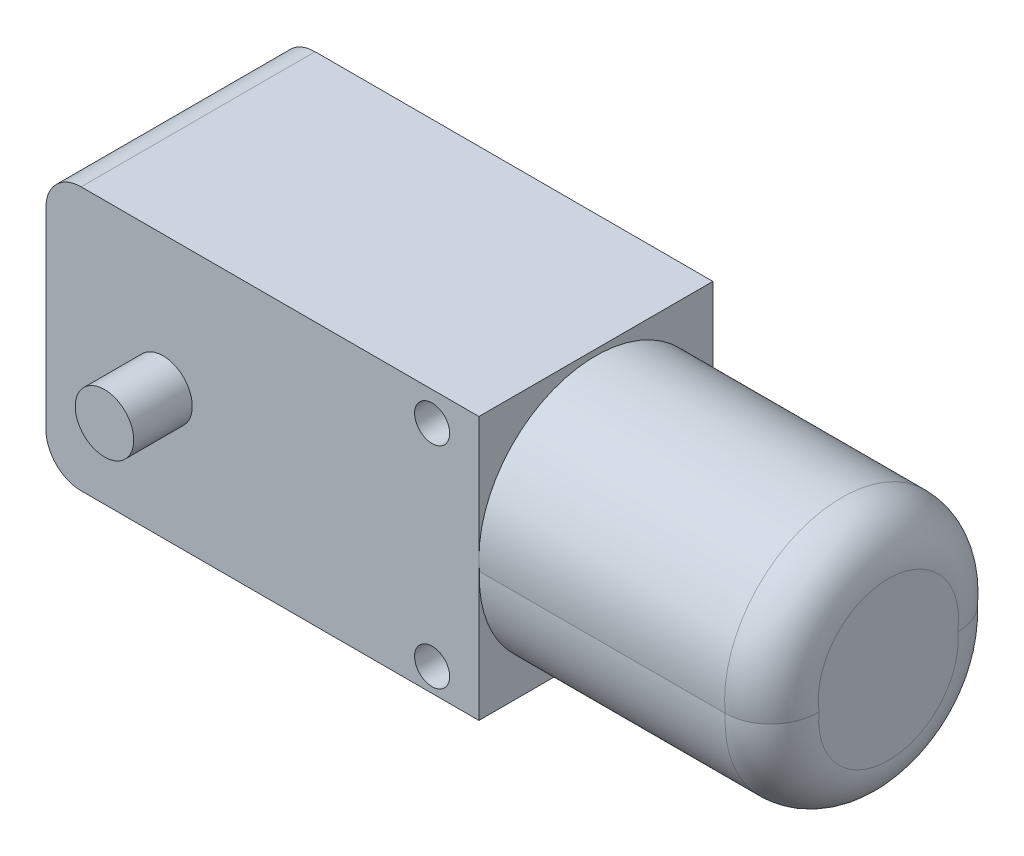
SolidWorks part; units mm, degrees
ref_plane "Front Plane" through (0, 0, 0) normal (0, 0, 1) x (1, 0, 0)
ref_plane "Top Plane" through (0, 0, 0) normal (0, 1, 0) x (1, 0, 0)
ref_plane "Right Plane" through (0, 0, 0) normal (1, 0, 0) x (0, 0, -1)
sketch "Sketch1" plane through (0, 0, 0) normal (0, 0, 1) x (1, 0, 0)
  line L1 (-64.2641, -2.5) -> (-27.2641, -2.5)
  line L2 (-64.2641, -2.5) -> (-64.2641, -25)
  line L3 (-64.2641, -25) -> (-27.2641, -25)
  line L4 (-27.2641, -2.5) -> (-27.2641, -25)
  dimension "D1" = 22.5
  dimension "D2" = 37
extrude "Boss-Extrude1" add sketch "Sketch1" against normal blind 20
sketch "Sketch2" plane through (-27.2641, 0, 0) normal (1, 0, 0) x (0, 0, -1)
  line L0 (20, -25) -> (0, -25) construction
  line L1 (20, -2.5) -> (0, -2.5) construction
  arc A0 (0.0501, -14) -> (19.9499, -14) centre (10, -14.5) ccw
  arc A1 (19.9499, -14) -> (0.0501, -14) centre (10, -13) ccw
  dimension "D2" = 12
  dimension "D1" = 12
extrude "Boss-Extrude2" add sketch "Sketch2" along normal blind 25
sketch "Sketch3" plane through (0, 0, 0) normal (0, 0, 1) x (1, 0, 0)
  circle A0 centre (-54.2641, -14) radius 2.5
  dimension "D1" = 5
extrude "Boss-Extrude3" add sketch "Sketch3" along normal blind 5
sketch "Sketch4" plane through (0, 0, -20) normal (0, 0, -1) x (-1, 0, 0)
  circle A1 centre (54.2641, -14) radius 2.5
  circle A2 centre (54.2641, -14) radius 2.5
  dimension "D1" = 0
extrude "Boss-Extrude4" add sketch "Sketch4" along normal blind 5
fillet "Fillet1" radius 3 2 edges at (-64.2641, -2.5, -10) (-64.2641, -25, -10)
fillet "Fillet2" radius 4 2 edges at (-2.2641, -3, -10) (-2.2641, -24.4624, -10)
sketch "Sketch5" plane through (-64.2641, 0, 0) normal (-1, 0, 0) x (0, 0, 1)
  line L0 (-10, -25) -> (-10, -2.5) construction
  line L1 (-8.625, -16.25) -> (-11.375, -16.25)
  line L2 (-8.625, -16.25) -> (-8.625, -11.25)
  line L3 (-8.625, -11.25) -> (-11.375, -11.25)
  line L4 (-11.375, -16.25) -> (-11.375, -11.25)
  line L5 (0, -25) -> (-20, -25) construction
  line L6 (0, -13.75) -> (-20, -13.75) construction
  line L7 (0, -5.5) -> (0, -22) construction
  line L8 (-20, -5.5) -> (-20, -22) construction
  dimension "D1" = 2.75
  dimension "D2" = 5
  dimension "D3" = 2.5
  dimension "D4" = 1.375
extrude "Boss-Extrude5" add sketch "Sketch5" along normal blind 5
sketch "Sketch6" plane through (0, 0, -11.375) normal (0, 0, -1) x (-1, 0, 0)
  line L1 (69.2641, -11.25) -> (64.2641, -11.25) construction
  line L2 (69.2641, -11.25) -> (69.2641, -16.25) construction
  circle A0 centre (66.7641, -13.75) radius 1.5
  dimension "D1" = 3
  dimension "D2" = 2.5
  dimension "D3" = 2.5
extrude "Cut-Extrude1" cut sketch "Sketch6" against normal up to surface (2.75 mm away) up to face at (-66.7641, -13.75, -8.625)
sketch "Sketch7" plane through (0, 0, -20) normal (0, 0, -1) x (-1, 0, 0)
  line L0 (6.2641, -14) -> (27.2641, -14) construction
  line L1 (27.2641, -13) -> (27.2641, -2.5) construction
  line L2 (27.2641, -25) -> (27.2641, -13) construction
  circle A0 centre (31.2641, -5) radius 1.5
  circle A1 centre (31.2641, -23) radius 1.5
  dimension "D1" = 9
  dimension "D2" = 18
  dimension "D3" = 4
  dimension "D4" = 4
extrude "Cut-Extrude2" cut sketch "Sketch7" against normal through all
